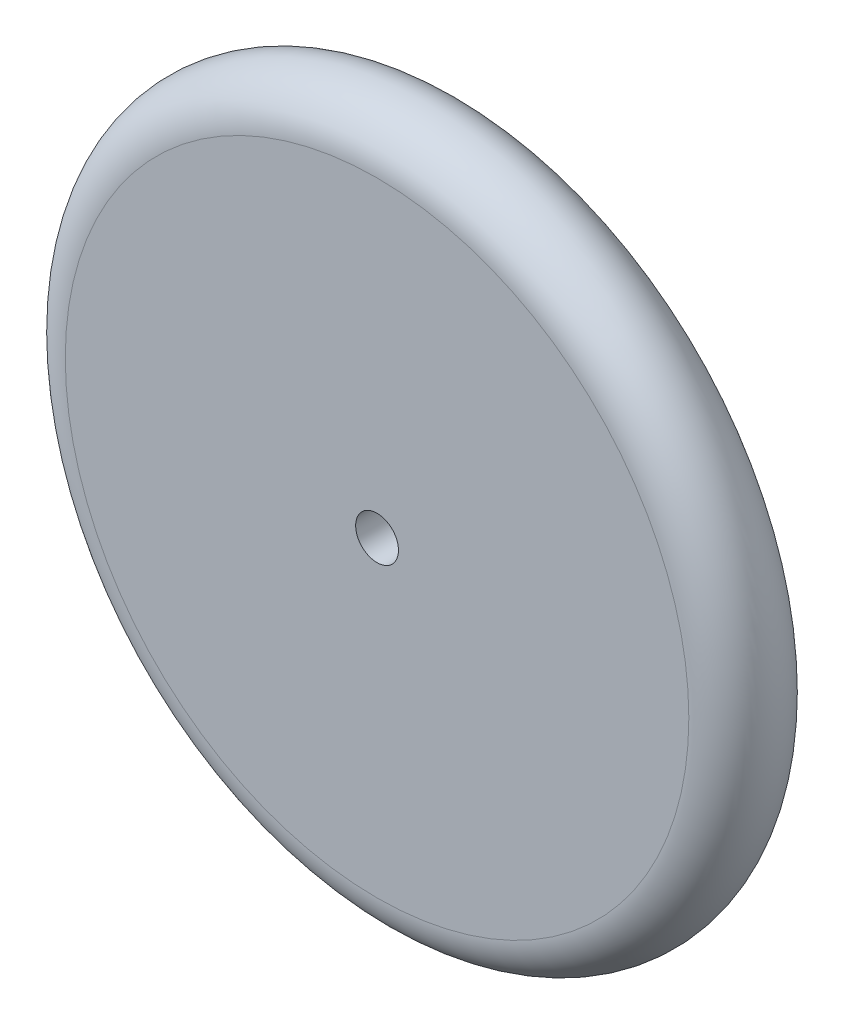
SolidWorks part; units mm, degrees
ref_plane "Front Plane" through (0, 0, 0) normal (0, 0, 1) x (1, 0, 0)
ref_plane "Top Plane" through (0, 0, 0) normal (0, 1, 0) x (1, 0, 0)
ref_plane "Right Plane" through (0, 0, 0) normal (1, 0, 0) x (0, 0, -1)
sketch "Sketch1" plane through (0, 0, 0) normal (0, 0, 1) x (1, 0, 0)
  circle A0 centre (0, 0) radius 158.75
  circle A1 centre (0, 0) radius 9.525
  dimension "D1" = 317.5
  dimension "D2" = 19.05
extrude "Boss-Extrude1" add sketch "Sketch1" along normal blind 40
fillet "Fillet1" 2 edges at (158.75, 0, 40) (158.75, 0, 0) type full round first side face at (158.75, 0, 40) second side face at (158.75, 0, 0) middle face at (158.75, 0, 40)
